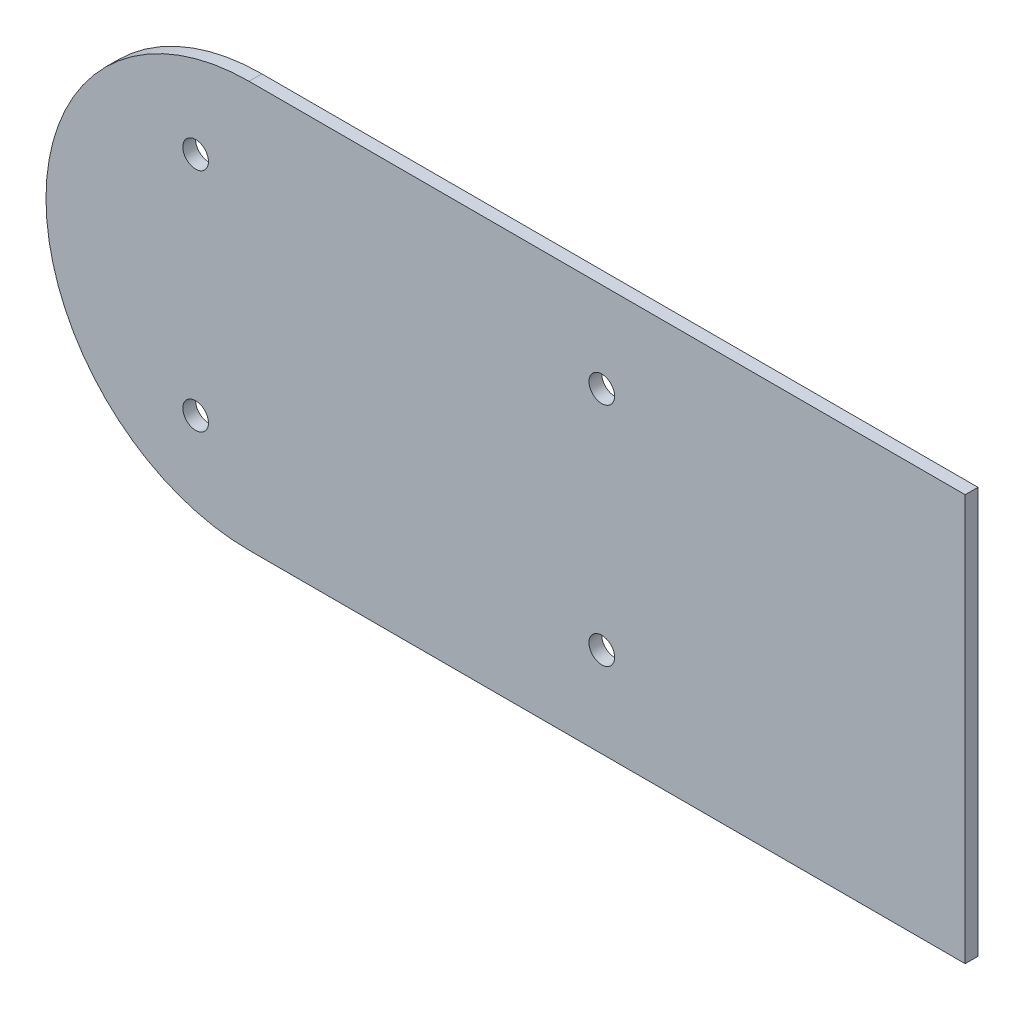
SolidWorks part; units mm, degrees
ref_plane "Front Plane" through (0, 0, 0) normal (0, 0, 1) x (1, 0, 0)
ref_plane "Top Plane" through (0, 0, 0) normal (0, 1, 0) x (1, 0, 0)
ref_plane "Right Plane" through (0, 0, 0) normal (1, 0, 0) x (0, 0, -1)
sketch "Sketch1" plane through (0, 0, 0) normal (0, 0, 1) x (1, 0, 0)
  line L0 (55, 0) -> (-55, 0) construction
  line L1 (-145, 52.92) -> (45, 52.92) construction
  line L2 (-145, 52.92) -> (-145, -52.92) construction
  line L3 (-145, -52.92) -> (45, -52.92) construction
  line L4 (45, 52.92) -> (45, -52.92) construction
  line L7 (215, -95) -> (-215, -95)
  line L8 (215, -95) -> (215, 95)
  line L9 (215, 95) -> (-215, 95)
  line L10 (-215, -95) -> (-215, 95)
  line L11 (215, -95) -> (-215, 95) construction
  line L12 (215, 95) -> (-215, -95) construction
  circle A0 centre (-145, 52.92) radius 6
  circle A1 centre (45, 52.92) radius 6
  circle A2 centre (45, -52.92) radius 6
  circle A3 centre (-145, -52.92) radius 6
  point P4 (-145, 0)
  point P14 (0, 0)
  dimension "D3" = 12
  dimension "D1" = 105.84
  dimension "D2" = 190
  dimension "D4" = 430
  dimension "D5" = 190
  dimension "D6" = 70
extrude "Boss-Extrude1" add sketch "Sketch1" along normal blind 6
fillet "Fillet1" radius 95 2 edges at (-215, -95, 3) (-215, 95, 3)
